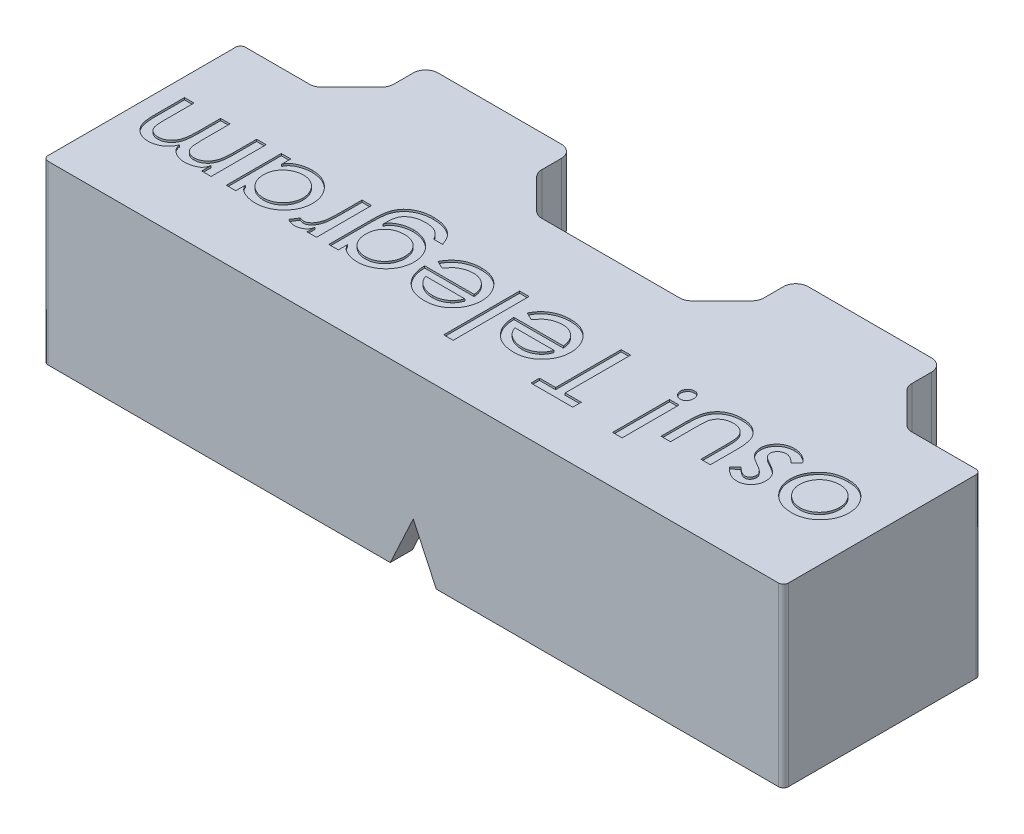
SolidWorks part; units mm, degrees
ref_plane "Front Plane" through (0, 0, 0) normal (0, 0, 1) x (1, 0, 0)
ref_plane "Top Plane" through (0, 0, 0) normal (0, 1, 0) x (1, 0, 0)
ref_plane "Right Plane" through (0, 0, 0) normal (1, 0, 0) x (0, 0, -1)
sketch "Sketch1" plane through (0, 0, 0) normal (0, 1, 0) x (1, 0, 0)
  line L0 (0, 0) -> (60, 0)
  line L1 (60, 0) -> (60, -16)
  line L2 (60, -16) -> (0, -16)
  line L3 (0, -16) -> (0, 0)
  point P3 (60, -20.5746)
  dimension "D1" = 60
  dimension "D2" = 16
extrude "Boss-Extrude1" add sketch "Sketch1" against normal blind 6.5
ref_plane "Plane1" through (15, 0, 0) normal (-1, 0, 0) x (0, 0, 1)
ref_plane "Plane2" through (45, 0, 0) normal (1, 0, 0) x (0, 0, -1)
sketch "Sketch2" plane through (15, 0, 0) normal (-1, 0, 0) x (0, 0, 1)
  line L0 (0, -6.5) -> (16, -6.5) construction
  line L1 (12.5, -6.5) -> (3.5, -6.5)
  arc A0 (3.5, -6.5) -> (12.5, -6.5) centre (8, -6.5) cw
  point P3 (0, 0)
  point P6 (0, 0)
  point P7 (8, -6.5)
  dimension "D1" = 9
extrude "Cut-Extrude1" cut sketch "Sketch2" against normal blind 11 and the other way blind 11
sketch "Sketch3" plane through (45, 0, 0) normal (1, 0, 0) x (0, 0, -1)
  line L0 (-12.5, -6.5) -> (-3.5, -6.5) construction
  line L1 (-12.5, -6.5) -> (-3.5, -6.5)
  arc A0 (-3.5, -6.5) -> (-12.5, -6.5) centre (-8, -6.5) ccw construction
  arc A1 (-3.5, -6.5) -> (-12.5, -6.5) centre (-8, -6.5) ccw
extrude "Cut-Extrude5" cut sketch "Sketch3" against normal blind 11 and the other way blind 11
sketch "Sketch4" plane through (0, -6.5, 0) normal (0, -1, 0) x (1, 0, 0)
  line L0 (1.8, 0) -> (1.8, 14.2)
  line L1 (60, 0) -> (0, 0) construction
  line L2 (1.8, 14.2) -> (58.2, 14.2)
  line L3 (58.2, 14.2) -> (58.2, 0)
  line L4 (58.2, 0) -> (60, 0)
  line L5 (60, 0) -> (60, 16)
  line L6 (60, 16) -> (0, 16)
  line L7 (0, 16) -> (0, 0)
  line L8 (0, 0) -> (1.8, 0)
  dimension "D1" = 1.8
  dimension "D2" = 1.8
extrude "Boss-Extrude2" add sketch "Sketch4" along normal blind 7.8
sketch "Sketch5" plane through (0, 0, 0) normal (0, 0, -1) x (-1, 0, 0)
  line L0 (-51, -6.5) -> (-51, -5.5)
  line L1 (-58.2, -6.5) -> (-1.8, -6.5) construction
  line L2 (-51, -5.5) -> (-39, -5.5)
  line L3 (-39, -5.5) -> (-39, -6.5)
  line L4 (-1.8, -6.5) -> (-58.2, -6.5) construction
  line L5 (-39, -6.5) -> (-51, -6.5)
  line L6 (-21, -6.5) -> (-21, -5.5)
  line L7 (-21, -5.5) -> (-9, -5.5)
  line L8 (-9, -5.5) -> (-9, -6.5)
  line L9 (-9, -6.5) -> (-21, -6.5)
  line L10 (-56, -6.5) -> (-34, -6.5) construction
  line L12 (-4, -6.5) -> (-26, -6.5) construction
  point P14 (-45, -6.5)
  point P15 (-45, -6.5)
  point P18 (-15, -6.5)
  point P19 (-15, -6.5)
  dimension "D1" = 1
  dimension "D2" = 12
extrude "Cut-Extrude6" cut sketch "Sketch5" against normal blind 8
sketch "Sketch6" plane through (0, 0, 0) normal (0, 0, -1) x (-1, 0, 0)
  line L0 (-51, -5.5) -> (-39, -5.5)
  line L1 (-39, -5.5) -> (-39, 0)
  line L2 (-60, 0) -> (0, 0) construction
  line L3 (-39, 0) -> (-51, 0)
  line L4 (-51, 0) -> (-51, -5.5)
  line L5 (-21, -5.5) -> (-9, -5.5)
  line L6 (-9, -5.5) -> (-9, 0)
  line L7 (-9, 0) -> (-21, 0)
  line L8 (-21, 0) -> (-21, -5.5)
extrude "Boss-Extrude3" add sketch "Sketch6" along normal blind 6
fillet "Fillet1" radius 1 8 edges at (9, -5.9968, 3.5282) (21, -5.9968, 3.5282) (51, -5.9968, 3.5282) (39, -5.9968, 3.5282) (26, -2, 8) (4, -2, 8) (34, -2, 8) (56, -2, 8)
chamfer "Chamfer1" distance 3 angle 45 4 edges at (9, -2.75, 0) (21, -2.75, 0) (51, -2.75, 0) (39, -2.75, 0)
fillet "Fillet2" radius 1 12 edges at (51, -2.75, -6) (9, -2.75, -6) (21, -2.75, -6) (39, -2.75, -6) (9, -2.75, -3) (6, -2.75, 0) (21, -2.75, -3) (24, -2.75, 0) (36, -2.75, 0) (39, -2.75, -3) (51, -2.75, -3) (54, -2.75, 0)
fillet "Fillet3" radius 0.4 12 edges at (0, -7.15, 16) (60, -7.15, 16) (60, -7.15, 0) (58.2, -10.4, 0) (58.2, -10.4, 14.2) (1.8, -10.4, 14.2) (1.8, -10.4, 0) (0, -7.15, 0) (9, -6, 0) (21, -6, 0) (39, -6, 0) (51, -6, 0)
sketch "Sketch7" plane through (0, 0, 0) normal (0, 1, 0) x (1, 0, 0)
  line L0 (60, -6) -> (0, -6) construction
  line L1 (0.4, -16) -> (59.6, -16) construction
  text T0 "<b>osu! Telegram</b>" font "Century Gothic" height 6
  point P7 (30, -16)
  point P8 (30, -6)
  dimension "D1" = 60
  dimension "D2" = 10
extrude "Cut-Extrude7" cut sketch "Sketch7" against normal blind 0.16
sketch "Sketch8" plane through (0, 0, 16) normal (0, 0, 1) x (1, 0, 0)
  line L0 (28.1348, -14.3) -> (30, -10.3)
  line L1 (59.6, -14.3) -> (0.4, -14.3) construction
  line L2 (30, -10.3) -> (31.8652, -14.3)
  line L3 (31.8652, -14.3) -> (28.1348, -14.3)
  point P4 (30, -14.3)
  point P6 (30, -14.3)
  point P7 (0, 0)
  dimension "D1" = 4
  dimension "D2" = 50
extrude "Cut-Extrude8" cut sketch "Sketch8" against normal up to next
